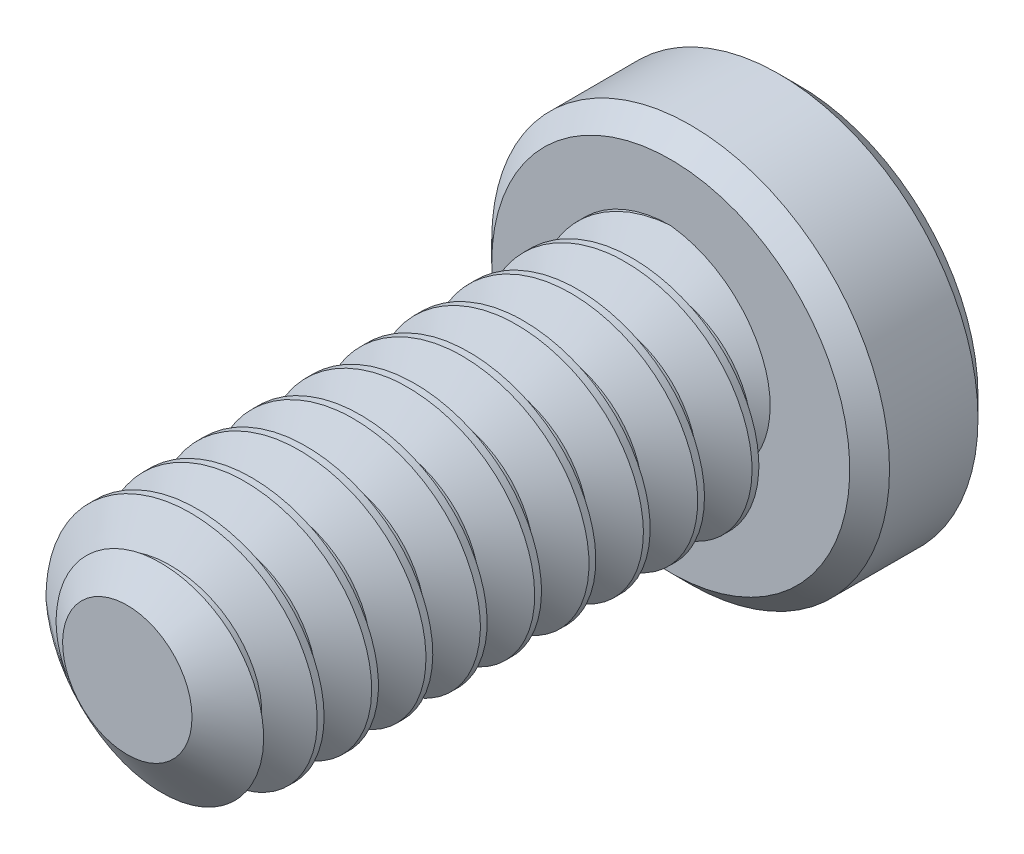
SolidWorks part; units mm, degrees
other "DetailItem1"
ref_plane "Front Plane" through (0, 0, 0) normal (0, 0, 1) x (1, 0, 0)
ref_plane "Top Plane" through (0, 0, 0) normal (0, 1, 0) x (1, 0, 0)
ref_plane "Right Plane" through (0, 0, 0) normal (1, 0, 0) x (0, 0, -1)
sketch "Sketch1" plane through (0, 0, 0) normal (0, 0, 1) x (1, 0, 0)
  circle A0 centre (0, 0) radius 1.4224
  dimension "OD" = 2.8448
extrude "Extrude1" add sketch "Sketch1" against normal blind 6.35
sketch "Sketch2" plane through (0, 0, 0) normal (0, 0, 1) x (1, 0, 0)
  circle A0 centre (0, 0) radius 1.4224 construction
  circle A1 centre (0, 0) radius 1.4224
curve "Helix/Spiral1" pitch 0.635 height 6.985 radius 1.4224 centre (0, 0, 0) axis (0, 0, -1) start towards (0, 1, 0) parameters "pitch"=0.635
sketch "Sketch3" plane through (0, 0, 0) normal (1, 0, 0) x (0, 0, -1)
  line L0 (-0.5556, 1.4224) -> (-0.3175, 1.01)
  line L1 (-0.3175, 1.01) -> (-0.2381, 1.01)
  line L2 (-0.2381, 1.01) -> (0, 1.4224)
  line L3 (-0.5556, 1.4224) -> (0, 1.4224)
  line L4 (-0.2778, 1.4224) -> (-0.2778, 1.01) construction
  line L5 (-0.4366, 1.2162) -> (-0.1191, 1.2162) construction
  line L6 (0, 1.4224) -> (0, -1.4224) construction
  dimension "D1" = 0.0794
  dimension "D2" = 0.3175
  dimension "D3" = 60
sweep "Cut-Sweep1" cut profiles "Sketch3" path "Helix/Spiral1" align with end faces yes
sketch "Sketch4" plane through (0, 0, 0) normal (1, 0, 0) x (0, 0, -1)
  line L0 (0.4666, 1.4224) -> (0, 0.756)
  line L1 (0, 0.756) -> (0, 1.4224)
  line L2 (0.4666, 1.4224) -> (0, 1.4224)
  line L3 (-0.5556, 1.4224) -> (0, 1.4224) construction
  line L4 (0, 0) -> (7.0209, 0) construction
  dimension "D1" = 55
  dimension "D2" = 0.254
revolve "Cut-Revolve1" cut sketch "Sketch4" angle 360 about L4
sketch "Sketch6" plane through (0, 0, -6.35) normal (0, 0, -1) x (-1, 0, 0)
  circle A0 centre (0, 0) radius 2.3241
  dimension "head dia" = 4.6482
extrude "Extrude2" add sketch "Sketch6" along normal blind 1.4986
sketch "Sketch7" plane through (0, 0, -7.8486) normal (0, 0, -1) x (-1, 0, 0)
  line L1 (0, 0.7332) -> (-0.635, 0.3666)
  line L2 (-0.635, 0.3666) -> (-0.635, -0.3666)
  line L3 (-0.635, -0.3666) -> (0, -0.7332)
  line L4 (0, -0.7332) -> (0.635, -0.3666)
  line L5 (0.635, -0.3666) -> (0.635, 0.3666)
  line L6 (0.635, 0.3666) -> (0, 0.7332)
  circle A0 centre (0, 0) radius 0.635 construction
  dimension "hex dia" = 1.27
extrude "Cut-Extrude1" cut sketch "Sketch7" against normal blind 0.9525
sketch "Sketch8" plane through (0, 0, -7.8486) normal (0, 0, -1) x (-1, 0, 0)
  circle A0 centre (0, 0) radius 0.7332
extrude "Cut-Extrude2" cut sketch "Sketch8" against normal through all draft 45
chamfer "Chamfer1" distance 0.2324 angle 45 2 edges at (-2.3241, 0, -7.8486) (-2.3241, 0, -6.35)
sketch "Sketch10" plane through (0, 0, -6.35) normal (0, 0, 1) x (1, 0, 0)
  circle A1 centre (0, 0) radius 1.4224
  circle A2 centre (0, 0) radius 1.4224
  dimension "D1" = 0
ref_plane "Plane1" through (0, 0, 0) normal (0, 0, 1) x (1, 0, 0)
extrude "partial thread" [suppressed] add sketch "Sketch10" along normal up to surface (12.7 mm away) separate body up to plane "Plane1"
chamfer "Chamfer2" [suppressed] distance 0.0569 angle 45
combine bodies "Combine1" [suppressed] operation type add bodies to combine 107 108
sketch "Sketch9" plane through (0, 0, 0) normal (1, 0, 0) x (0, 0, -1)
  line L0 (0, 1.4224) -> (0, -1.4224) construction
  line L1 (1.5875, 1.4224) -> (1.5875, -1.4224) construction
  dimension "D1" = 1.5875
sketch "Sketch11" plane through (0, 0, -6.35) normal (0, 0, 1) x (1, 0, 0)
  circle A0 centre (0, 0) radius 3.175
  dimension "Shoulder Diameter" = 6.35
equation "\"D3@Helix/Spiral1\" = \"screw length@Extrude1\"+\"pitch@Helix/Spiral1\""
equation "\"D1@Sketch3\" = \"pitch@Helix/Spiral1\"*.125"
equation "\"D2@Sketch3\" = \"pitch@Helix/Spiral1\"*.5"
equation "\"D1@Cut-Extrude1\" = \"hex dia@Sketch7\"*.75"
equation "\"D1@Chamfer1\" = \"head dia@Sketch6\"*.05"
equation "\"D1@Sketch9\" = \"pitch@Helix/Spiral1\"*2.5"
equation "\"D1@Chamfer2\"=\"OD@Sketch1\"*.02"
